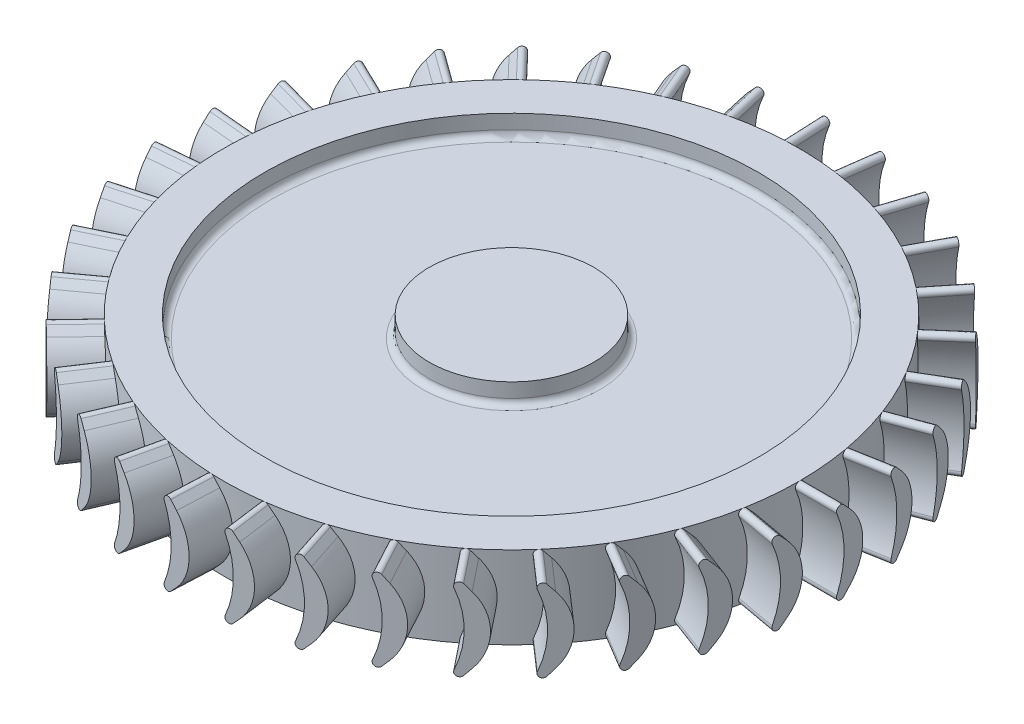
SolidWorks part; units mm, degrees
ref_plane "Front Plane" through (0, 0, 0) normal (0, 0, 1) x (1, 0, 0)
ref_plane "Top Plane" through (0, 0, 0) normal (0, 1, 0) x (1, 0, 0)
ref_plane "Right Plane" through (0, 0, 0) normal (1, 0, 0) x (0, 0, -1)
sketch "Sketch1" plane through (0, 0, 0) normal (0, 0, 1) x (1, 0, 0)
  line L0 (0, 0) -> (0, 10)
  line L1 (0, 10) -> (10, 10)
  line L3 (30, 7.5) -> (30, 10)
  line L4 (30, 10) -> (35, 10)
  line L5 (35, 10) -> (35, 0)
  line L6 (35, 0) -> (30, 0)
  line L7 (30, 0) -> (30, 2.5)
  line L9 (10, 0) -> (0, 0)
  line L10 (0, 5) -> (35, 5) construction
  line L11 (30, 7.5) -> (10, 7.5)
  line L12 (10, 7.5) -> (10, 10)
  line L13 (10, 0) -> (10, 2.5)
  line L14 (10, 2.5) -> (30, 2.5)
  dimension "D1" = 35
  dimension "D2" = 10
  dimension "D3" = 5
  dimension "D4" = 5
  dimension "D5" = 10
  dimension "D6" = 10
revolve "Revolve1" add sketch "Sketch1" angle 360 about L0
fillet "Fillet2" radius 0.762 4 edges at (0, 7.5, -10) (0, 7.5, -30) (0, 2.5, -10) (0, 2.5, -30)
ref_plane "Plane1" through (35, 0, 0) normal (1, 0, 0) x (0, 0, -1)
sketch "Sketch2" plane through (35, 0, 0) normal (1, 0, 0) x (0, 0, -1)
  line L0 (0, 0) -> (0, 10) construction
  line L1 (35, 10) -> (-35, 10) construction
  line L2 (0.3657, 9.841) -> (1.1043, 9.0489)
  line L3 (0.3657, 0.159) -> (1.1043, 0.9511)
  line L4 (-0.4603, 9.3046) -> (1.367, 5) construction
  line L5 (1.367, 5) -> (-0.4603, 0.6954) construction
  line L6 (2.6992, 5) -> (-4.6664, 4.8471) construction
  arc A0 (-0.4603, 9.3046) -> (-0.4603, 0.6954) centre (-10.6013, 5) cw
  arc A1 (-0.4603, 9.3046) -> (0.3657, 9.841) centre (0, 9.5) cw
  arc A2 (-0.4603, 0.6954) -> (0.3657, 0.159) centre (0, 0.5) ccw
  arc A3 (1.1043, 9.0489) -> (1.1043, 0.9511) centre (-3.2377, 5) cw
  arc A4 (-4.9723, 6.8869) -> (-5.0769, 2.8257) centre (-10.6013, 5) cw construction
  point P18 (-3.7958, 7.6046)
  point P20 (-4.6664, 4.8471)
  dimension "D1" = 0.5
  dimension "D2" = 0.5
  dimension "D3" = 23
  dimension "D4" = 20
  dimension "D5" = 20
  dimension "D6" = 5.08
extrude "Boss-Extrude1" add sketch "Sketch2" along normal blind 5 and the other way blind 2.54
pattern_circular "CirPattern1" count 35 over 360 about axis through (0, 10, 0) along (0, 1, 0) of "Boss-Extrude1"
equation "\"D5@Sketch2\"=\"D4@Sketch2\""
